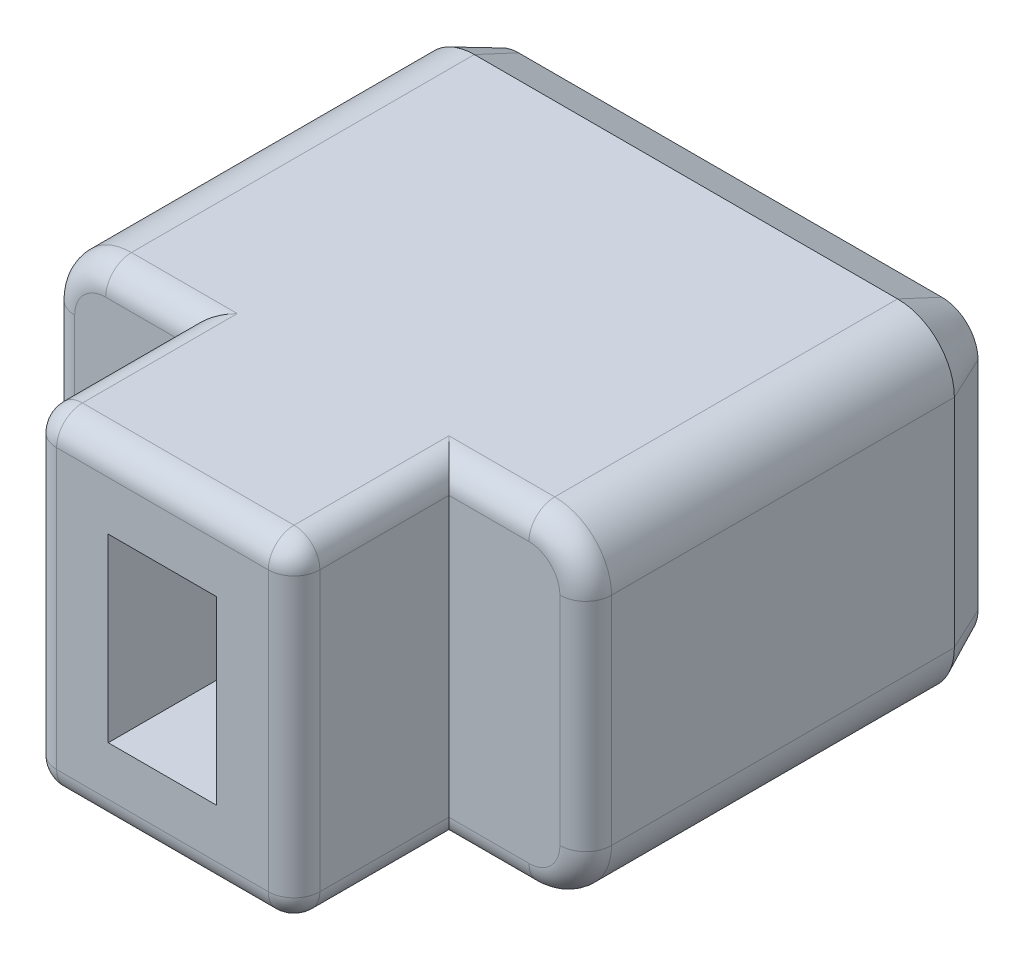
SolidWorks part; units mm, degrees
ref_plane "Plan de face" through (0, 0, 0) normal (0, 0, 1) x (1, 0, 0)
ref_plane "Plan de dessus" through (0, 0, 0) normal (0, 1, 0) x (1, 0, 0)
ref_plane "Plan de droite" through (0, 0, 0) normal (1, 0, 0) x (0, 0, -1)
sketch "Esquisse2" plane through (0, 0, 0) normal (0, 0, 1) x (1, 0, 0)
  line L1 (1.1, 0) -> (9.3, 0)
  line L2 (0, 1.1) -> (0, 5.3)
  line L3 (1.1, 6.4) -> (9.3, 6.4)
  line L4 (10.4, 1.1) -> (10.4, 5.3)
  arc A0 (9.3, 6.4) -> (10.4, 5.3) centre (9.3, 5.3) cw
  arc A1 (9.3, 0) -> (10.4, 1.1) centre (9.3, 1.1) ccw
  arc A2 (1.1, 0) -> (0, 1.1) centre (1.1, 1.1) cw
  arc A3 (0, 5.3) -> (1.1, 6.4) centre (1.1, 5.3) cw
  point P7 (10.4, 6.4)
  point P12 (0, 0)
  point P15 (0, 6.4)
  dimension "D3" = 1.1
  dimension "D1" = 10.4
  dimension "D2" = 6.4
extrude "Boss.-Extru.1" add sketch "Esquisse2" along normal blind 11
sketch "Esquisse3" plane through (0, 0, 11) normal (0, 0, 1) x (1, 0, 0)
  line L0 (0, 5.3) -> (0, 1.1) construction
  line L1 (4.15, 4.95) -> (6.25, 4.95)
  line L2 (4.15, 4.95) -> (4.15, 1.45)
  line L3 (4.15, 1.45) -> (6.25, 1.45)
  line L4 (6.25, 4.95) -> (6.25, 1.45)
  line L5 (10.4, 1.1) -> (10.4, 5.3) construction
  line L6 (9.3, 6.4) -> (1.1, 6.4) construction
  line L7 (1.1, 0) -> (9.3, 0) construction
  dimension "D1" = 2.1
  dimension "D2" = 3.5
  dimension "D3" = 4.15
  dimension "D4" = 4.15
  dimension "D5" = 1.45
  dimension "D6" = 1.45
extrude "Enlèv. mat.-Extru.1" cut sketch "Esquisse3" against normal blind 3
sketch "Esquisse4" plane through (0, 0, 11) normal (0, 0, 1) x (1, 0, 0)
  line L0 (2.65, 6.4) -> (2.65, 0)
  line L1 (9.3, 6.4) -> (1.1, 6.4) construction
  line L2 (1.1, 0) -> (9.3, 0) construction
  line L3 (2.65, 0) -> (7.75, 0)
  line L4 (7.75, 0) -> (7.75, 6.4)
  line L5 (7.75, 6.4) -> (2.65, 6.4)
  line L6 (4.15, 4.95) -> (4.15, 1.45) construction
  line L7 (6.25, 1.45) -> (6.25, 4.95) construction
  dimension "D1" = 1.5
  dimension "D2" = 1.5
extrude "Enlèv. mat.-Extru.2" cut sketch "Esquisse4" against normal blind 3 flip side to cut
fillet "Congé1" radius 0.5 18 edges at (8.525, 0, 8) (10.0778, 0.3222, 8) (10.4, 3.2, 8) (10.0778, 6.0778, 8) (1.875, 6.4, 8) (0.3222, 6.0778, 8) (1.875, 0, 8) (0.3222, 0.3222, 8) (7.75, 6.4, 9.5) (2.65, 6.4, 9.5) (7.75, 0, 9.5) (2.65, 0, 9.5) (2.65, 3.2, 11) (5.2, 6.4, 11) (7.75, 3.2, 11) (5.2, 0, 11) (8.525, 6.4, 8) (0, 3.2, 8)
chamfer "Chanfrein1" distance 0.4 angle 65 8 edges at (5.2, 0, 0) (10.0778, 0.3222, 0) (0.3222, 0.3222, 0) (10.4, 3.2, 0) (0, 3.2, 0) (10.0778, 6.0778, 0) (0.3222, 6.0778, 0) (5.2, 6.4, 0) first distance on face at (5.2, 3.2, 0)
sketch "Esquisse5" plane through (0, 0, 0) normal (0, 0, -1) x (-1, 0, 0)
  line L0 (-0.4, 5.3) -> (-10, 5.3) construction
  arc A0 (-9.3, 6) -> (-10, 5.3) centre (-9.3, 5.3) ccw construction
  text T0 "7" font "Century Gothic" height 4
extrude "Enlèv. mat.-Extru.3" cut sketch "Esquisse5" against normal blind 0.3
extrude "Boss.-Extru.2" add sketch "Esquisse5<2>" along normal blind 0.3 separate body
sketch "Esquisse5<2>" plane through (0, 0, 0) normal (0, 0, -1) x (-1, 0, 0) same geometry as "Esquisse5"
